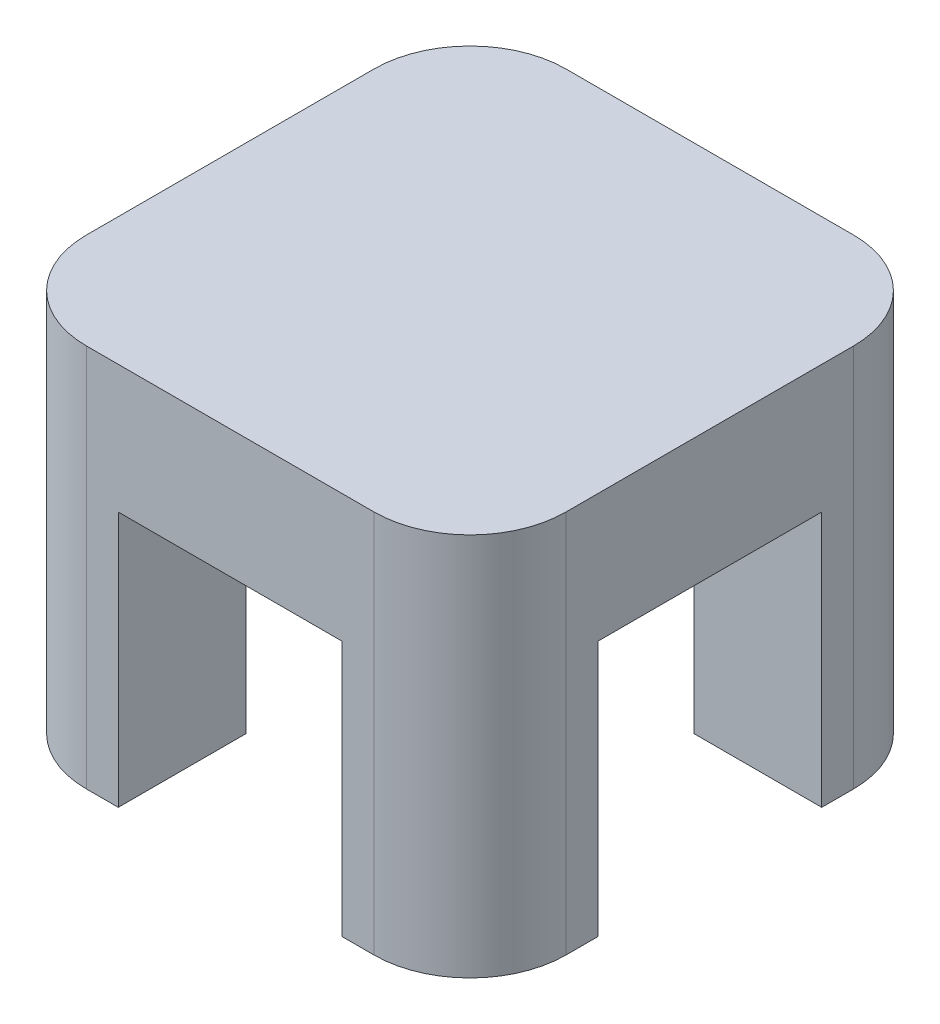
SolidWorks part; units mm, degrees
ref_plane "Alzado" through (0, 0, 0) normal (0, 0, 1) x (1, 0, 0)
ref_plane "Planta" through (0, 0, 0) normal (0, 1, 0) x (1, 0, 0)
ref_plane "Vista lateral" through (0, 0, 0) normal (1, 0, 0) x (0, 0, -1)
sketch "Croquis1" plane through (0, 0, 0) normal (0, 1, 0) x (1, 0, 0)
  line L1 (75, 75) -> (-75, 75)
  line L2 (75, 75) -> (75, -75)
  line L3 (75, -75) -> (-75, -75)
  line L4 (-75, 75) -> (-75, -75)
  line L5 (75, 75) -> (-75, -75) construction
  line L6 (75, -75) -> (-75, 75) construction
  point P0 (0, 0)
  dimension "D1" = 150
  dimension "D2" = 150
extrude "Saliente-Extruir1" add sketch "Croquis1" along normal blind 40
sketch "Croquis2" plane through (0, 0, 0) normal (0, -1, 0) x (-1, 0, 0)
  line L1 (75, -75) -> (35, -75)
  line L2 (75, -75) -> (75, -35)
  line L3 (75, -35) -> (35, -35)
  line L4 (35, -75) -> (35, -35)
  line L5 (-75, -75) -> (-35, -75)
  line L6 (-75, -75) -> (-75, -35)
  line L7 (-75, -35) -> (-35, -35)
  line L8 (-35, -75) -> (-35, -35)
  line L9 (75, 75) -> (35, 75)
  line L10 (75, 75) -> (75, 35)
  line L11 (75, 35) -> (35, 35)
  line L12 (35, 75) -> (35, 35)
  line L13 (-75, 75) -> (-35, 75)
  line L14 (-75, 75) -> (-75, 35)
  line L15 (-75, 35) -> (-35, 35)
  line L16 (-35, 75) -> (-35, 35)
  dimension "D1" = 40
  dimension "D2" = 40
  dimension "D3" = 40
  dimension "D4" = 40
  dimension "D5" = 40
  dimension "D6" = 40
  dimension "D7" = 40
  dimension "D8" = 40
extrude "Saliente-Extruir2" add sketch "Croquis2" along normal blind 80
fillet "Redondeo1" radius 30 4 edges at (-75, -20, -75) (75, -20, -75) (75, -20, 75) (-75, -20, 75)
